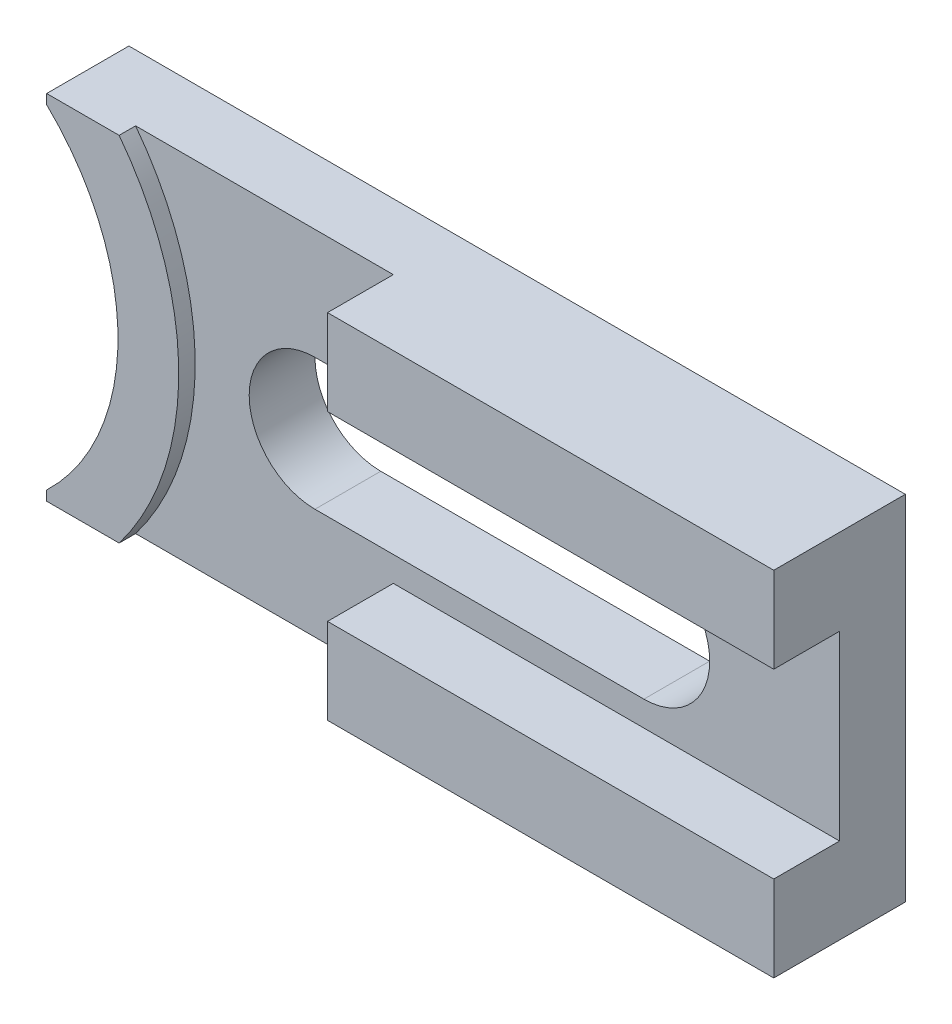
SolidWorks part; units mm, degrees
note: The reader was unsure of these and kept them because the rebuilt part matched: shared geometry of "Sketch2<3>", "Sketch2<5>".
ref_plane "Front Plane" through (0, 0, 0) normal (0, 0, 1) x (1, 0, 0)
ref_plane "Top Plane" through (0, 0, 0) normal (0, 1, 0) x (1, 0, 0)
ref_plane "Right Plane" through (0, 0, 0) normal (1, 0, 0) x (0, 0, -1)
sketch "Sketch1" plane through (0, 0, 0) normal (0, 0, 1) x (1, 0, 0)
  line L12 (57.15, 3.175) -> (17.3112, 3.175)
  line L13 (-17.3112, 3.175) -> (-57.15, 3.175)
  line L14 (-57.15, 3.175) -> (-57.15, -3.175)
  line L15 (-57.15, -3.175) -> (-17.3112, -3.175)
  line L16 (17.3112, -3.175) -> (57.15, -3.175)
  line L17 (57.15, -3.175) -> (57.15, 3.175)
  circle A1 centre (0, 0) radius 11.25
  arc A4 (17.3112, 3.175) -> (-17.3112, 3.175) centre (0, 0) ccw
  arc A5 (-17.3112, -3.175) -> (17.3112, -3.175) centre (0, 0) ccw
sketch "Sketch2" plane through (0, 0, 0) normal (0, 0, 1) x (1, 0, 0)
  line L0 (17.247, 3.5071) -> (36.1288, 3.5071)
  line L1 (36.1288, 3.5071) -> (36.1288, 6.8172)
  line L2 (36.1288, 6.8172) -> (16.2261, 6.8172)
  line L3 (0, 0) -> (57.15, 0) construction
  line L4 (57.15, -3.175) -> (57.15, 3.175) construction
  line L5 (36.1288, -6.8172) -> (16.2261, -6.8172)
  line L6 (36.1288, -3.5071) -> (36.1288, -6.8172)
  line L7 (17.247, -3.5071) -> (36.1288, -3.5071)
  line L8 (0, 0) -> (0, 17.6) construction
  line L9 (6.1509, -16.4902) -> (6.1509, 16.4902)
  line L10 (36.1288, 6.8172) -> (16.2261, 6.8172)
  line L11 (36.1288, 6.8172) -> (36.1288, -6.8172)
  line L12 (36.1288, -6.8172) -> (16.2261, -6.8172)
  line L13 (16.2261, 6.8172) -> (16.2261, -6.8172)
  line L14 (16.2261, 6.8172) -> (6.1509, 6.8172)
  line L15 (16.2261, -6.8172) -> (6.1509, -6.8172)
  line L16 (18.8996, -6.8172) -> (18.8996, 6.8172)
  circle A0 centre (0, 0) radius 17.6
  circle A1 centre (0, 0) radius 8.905
  circle A2 centre (0, 0) radius 11.25 construction
  circle A3 centre (0, 0) radius 11.25
extrude "Boss-Extrude1" add sketch "Sketch2" along normal blind 2.54 contours A0 L0 L1 L2 | A0 L5 L6 L7
extrude "Boss-Extrude2" add sketch "Sketch2<3>" against normal blind 2.54 contours A1 L9 A0 L13 | A0 L13 | A0 L7 L11 L0 | A0 L5 L6 L7 | A0 L0 L1 L2 | A0 L12 L16 L7 | A0 L7 L16 L0 | A0 L0 L16 L10
sketch "Sketch2<3>" plane through (0, 0, 0) normal (0, 0, 1) x (1, 0, 0) same geometry as "Sketch2"
extrude "Boss-Extrude3" add sketch "Sketch2<5>" along normal blind 0.635 and the other way blind 2.54 contours L9 A3 A1
sketch "Sketch2<5>" plane through (0, 0, 0) normal (0, 0, 1) x (1, 0, 0) same geometry as "Sketch2"
sketch "Sketch3" plane through (0, 0, -2.54) normal (0, 0, -1) x (-1, 0, 0)
  line L0 (0, 0) -> (-36.1288, 0) construction
  line L1 (-28.575, 0) -> (-15.875, 0) construction
  line L2 (-28.575, 2.54) -> (-15.875, 2.54)
  line L3 (-28.575, -2.54) -> (-15.875, -2.54)
  line L5 (-36.1288, 6.8172) -> (-36.1288, -6.8172)
  line L6 (-36.1288, -6.8172) -> (-6.1509, -6.8172)
  line L7 (-6.1509, -6.8172) -> (-6.1509, -6.4393)
  line L8 (-6.1509, 6.4393) -> (-6.1509, 6.8172)
  line L9 (-6.1509, 6.8172) -> (-36.1288, 6.8172)
  line L10 (-36.1288, 6.8172) -> (-36.1288, -6.8172)
  line L11 (-36.1288, -6.8172) -> (-6.1509, -6.8172)
  line L12 (-6.1509, -6.8172) -> (-6.1509, -6.4393)
  line L13 (-6.1509, 6.4393) -> (-6.1509, 6.8172)
  line L14 (-6.1509, 6.8172) -> (-36.1288, 6.8172)
  arc A1 (-6.1509, 6.4393) -> (-6.1509, -6.4393) centre (0, 0) ccw
  arc A2 (-6.1509, 6.4393) -> (-6.1509, -6.4393) centre (0, 0) ccw
  arc A3 (-28.575, 2.54) -> (-28.575, -2.54) centre (-28.575, 0) ccw
  arc A4 (-15.875, -2.54) -> (-15.875, 2.54) centre (-15.875, 0) ccw
  point P8 (-22.225, 0)
  dimension "D2" = 2.54
  dimension "D3" = 28.575
  dimension "D4" = 12.7
  dimension "D1" = 0
extrude "Cut-Extrude2" cut sketch "Sketch3" against normal through all
sketch "Sketch4" plane through (0, 0, -2.54) normal (0, 0, -1) x (-1, 0, 0)
  line L0 (-36.1288, 0) -> (-31.115, 0) construction
  line L1 (-36.1288, 6.8172) -> (-36.1288, -6.8172) construction
  line L2 (-33.6219, 0) -> (-33.6219, -6.8172) construction
  line L3 (-36.1288, -6.8172) -> (-6.1509, -6.8172) construction
  line L4 (-33.6219, 0) -> (-33.6219, 6.8172) construction
  line L5 (-36.1288, 6.8172) -> (-6.1509, 6.8172) construction
  arc A0 (-28.575, 2.54) -> (-28.575, -2.54) centre (-28.575, 0) ccw construction
  text T0 "<b>SN104</b>" font "Century Gothic" height 2
extrude "Cut-Extrude3" cut sketch "Sketch4" against normal blind 0.5
